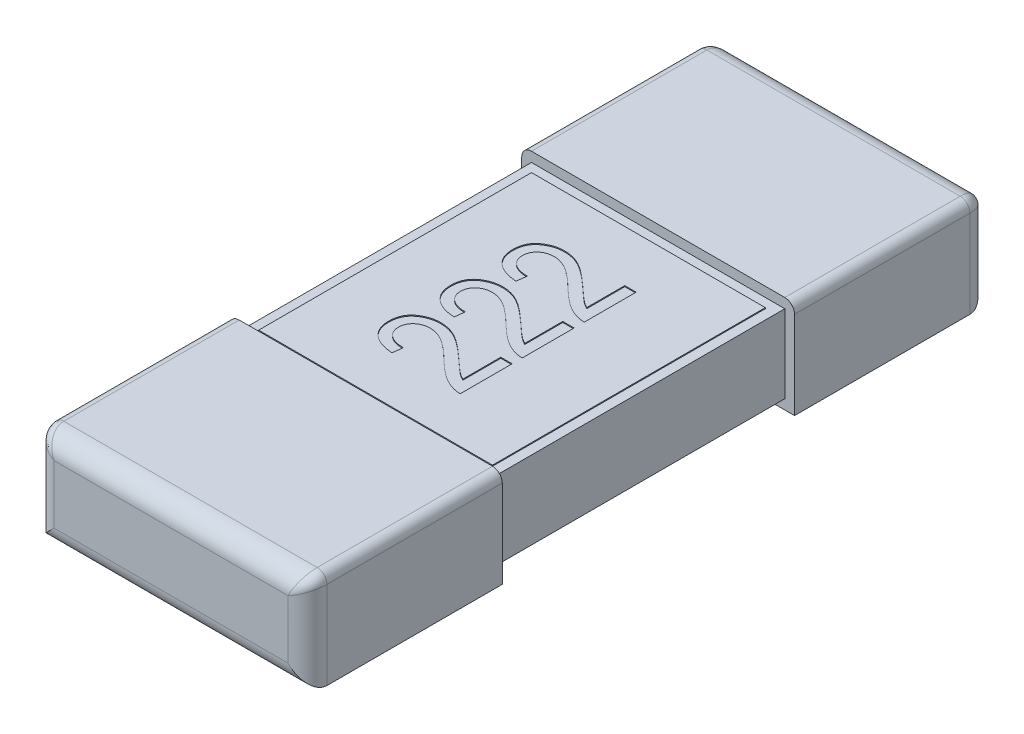
SolidWorks part; units mm, degrees
ref_plane "Front Plane" through (0, 0, 0) normal (0, 0, 1) x (1, 0, 0)
ref_plane "Top Plane" through (0, 0, 0) normal (0, 1, 0) x (1, 0, 0)
ref_plane "Right Plane" through (0, 0, 0) normal (1, 0, 0) x (0, 0, -1)
ref_plane "Plane1" through (0, 0, 0) normal (0, 0, 1) x (1, 0, 0)
sketch "Sketch1" plane through (0, 0, 0) normal (0, 0, 1) x (1, 0, 0)
  line L0 (-0.65, 0.5) -> (0.65, 0.5)
  line L1 (0.65, 0.5) -> (0.65, 0.1)
  line L2 (0.65, 0.1) -> (-0.65, 0.1)
  line L3 (-0.65, 0.1) -> (-0.65, 0.5)
  dimension "D1" = 0.1
  dimension "D2" = 0.4
  dimension "D3" = 1.3
  dimension "D4" = 0.65
extrude "Boss-Extrude1" add sketch "Sketch1" along normal blind 0.75 and the other way blind 0.75
sketch "Sketch2" plane through (0, 0, 0.75) normal (0, 0, 1) x (1, 0, 0)
  line L4 (0.7, 0.05) -> (-0.7, 0.05)
  line L5 (-0.7, 0.05) -> (-0.7, 0.5)
  line L6 (-0.65, 0.55) -> (0.65, 0.55)
  line L7 (0.7, 0.5) -> (0.7, 0.05)
  arc A2 (-0.65, 0.55) -> (-0.7, 0.5) centre (-0.65, 0.5) ccw
  arc A3 (0.7, 0.5) -> (0.65, 0.55) centre (0.65, 0.5) ccw
extrude "Boss-Extrude2" add sketch "Sketch2" along normal blind 1
fillet "Fillet1" radius 0.1 6 edges at (0, 0.05, 1.75) (-0.7, 0.275, 1.75) (-0.6854, 0.5354, 1.75) (0, 0.55, 1.75) (0.6854, 0.5354, 1.75) (0.7, 0.275, 1.75)
mirror "Mirror3" about plane through (0, 0, 0) normal (0, 0, 1) of "Boss-Extrude2", "Fillet1"
ref_plane "Plane2" through (0, 0, 0) normal (0, 1, 0) x (0, 0, 1)
sketch "Sketch4" plane through (0, 0.5, 0) normal (0, 1, 0) x (1, 0, 0)
  line L0 (-0.65, 0.75) -> (-0.65, -0.75) construction
  line L1 (-0.6, -0.7) -> (0.6, -0.7)
  line L2 (-0.6, -0.7) -> (-0.6, 0.7)
  line L3 (-0.6, 0.7) -> (0.6, 0.7)
  line L4 (0.6, -0.7) -> (0.6, 0.7)
  line L5 (0.2, 0.6255) -> (0.2, -0.7) construction
  text T0 "222 \r\n" font "Arial Narrow" height 0.5
  dimension "D1" = 0.05
  dimension "D2" = 1.2
  dimension "D3" = 1.4
  dimension "D4" = 0.7
  dimension "D5" = 0.4
  dimension "D6" = 0.63
extrude "Boss-Extrude4" add sketch "Sketch4" along normal blind 0.005
